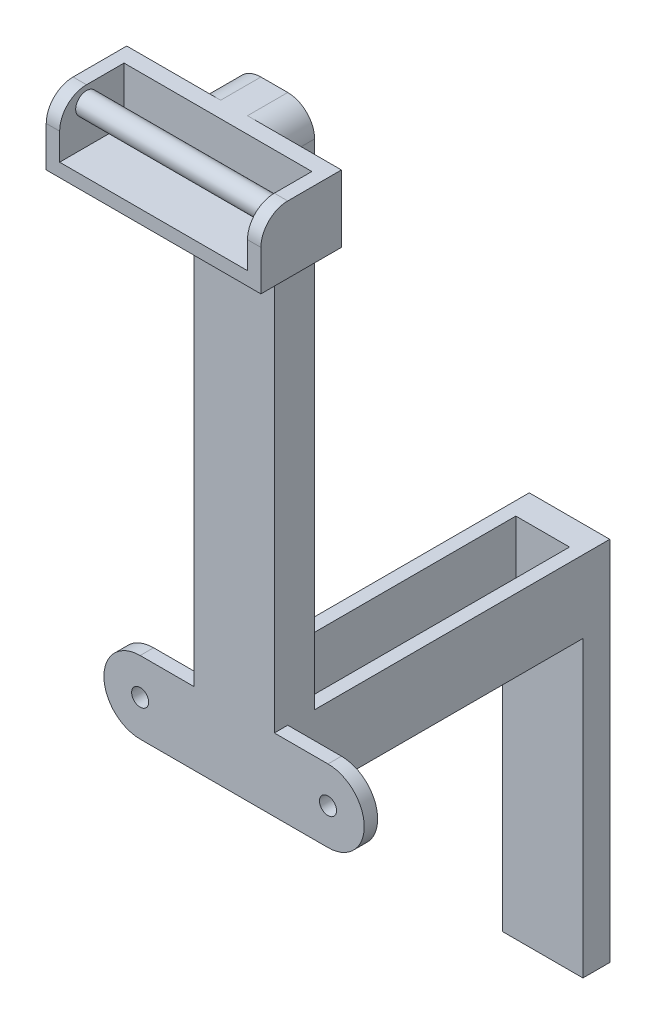
SolidWorks part; units mm, degrees
ref_plane "Front Plane" through (0, 0, 0) normal (0, 0, 1) x (1, 0, 0)
ref_plane "Top Plane" through (0, 0, 0) normal (0, 1, 0) x (1, 0, 0)
ref_plane "Right Plane" through (0, 0, 0) normal (1, 0, 0) x (0, 0, -1)
sketch "Sketch1" plane through (0, 0, 0) normal (0, 0, 1) x (1, 0, 0)
  line L0 (50, 212.065) -> (-20, 212.065) construction
  line L1 (30, -62.835) -> (0, -62.835)
  line L2 (30, -62.835) -> (30, 419.765)
  line L3 (30, 419.765) -> (0, 419.765)
  line L4 (0, -62.835) -> (0, 419.765)
  line L5 (30, -62.835) -> (0, 419.765) construction
  line L6 (30, 419.765) -> (0, -62.835) construction
  line L7 (50, 198.565) -> (-20, 198.565)
  line L8 (50, 225.565) -> (-20, 225.565)
  arc A0 (50, 198.565) -> (50, 225.565) centre (50, 212.065) ccw
  arc A1 (-20, 225.565) -> (-20, 198.565) centre (-20, 212.065) ccw
  point P0 (15, 178.465)
  point P7 (15, 212.065)
  dimension "D1" = 482.6
  dimension "D2" = 27
  dimension "D3" = 30
  dimension "D4" = 33.6
  dimension "D5" = 70
  dimension "D6" = 0
extrude "Extrude1" add sketch "Sketch1" along normal blind 15 contours L8 L2 L3 L4 | L7 A0 L8 L2 | L2 L8 L4 L7 | L8 A1 L7 L4 | L2 L7 L4 L1 region at (15, 67.865, 0) region at (15, 212.065, 0) region at (45.4498, 212.065, 0) region at (-15.4498, 212.065, 0) region at (15, 322.665, 0)
fillet "Fillet1" radius 10 4 edges at (30, -62.835, 7.5) (0, -62.835, 7.5) (0, 419.765, 7.5) (30, 419.765, 7.5)
sketch "Sketch2" plane through (0, 0, 0) normal (0, 0, -1) x (-1, 0, 0)
  line L0 (-50, 225.565) -> (-30, 225.565) construction
  line L1 (-50, 198.565) -> (-30, 198.565) construction
  line L2 (0, 198.565) -> (20, 198.565) construction
  line L3 (0, 225.565) -> (20, 225.565) construction
  line L4 (-50, 225.565) -> (-30, 225.565)
  line L5 (-50, 198.565) -> (-30, 198.565)
  line L6 (0, 198.565) -> (20, 198.565)
  line L7 (0, 225.565) -> (20, 225.565)
  line L8 (-30, 225.565) -> (-30, 198.565)
  line L9 (0, 225.565) -> (0, 198.565)
  arc A0 (20, 198.565) -> (20, 225.565) centre (20, 212.065) ccw construction
  arc A1 (-50, 225.565) -> (-50, 198.565) centre (-50, 212.065) ccw construction
  arc A2 (20, 198.565) -> (20, 225.565) centre (20, 212.065) ccw
  arc A3 (-50, 225.565) -> (-50, 198.565) centre (-50, 212.065) ccw
extrude "Extrude2" cut sketch "Sketch2" against normal blind 10
sketch "Sketch3" plane through (0, 0, 15) normal (0, 0, 1) x (1, 0, 0)
  line L0 (30, 407.265) -> (0, 407.265) construction
  line L1 (-25, 394.765) -> (55, 394.765)
  line L2 (-25, 394.765) -> (-25, 419.765)
  line L3 (-25, 419.765) -> (55, 419.765)
  line L4 (55, 394.765) -> (55, 419.765)
  line L5 (-25, 394.765) -> (55, 419.765) construction
  line L6 (-25, 419.765) -> (55, 394.765) construction
  line L7 (30, 225.565) -> (30, 409.765) construction
  line L8 (0, 225.565) -> (0, 409.765) construction
  line L9 (15, 407.265) -> (15, 419.765) construction
  line L10 (20, 419.765) -> (10, 419.765) construction
  point P0 (15, 407.265)
  dimension "D1" = 80
  dimension "D2" = 0
  dimension "D3" = 25
  dimension "D4" = 0
extrude "Extrude3" add sketch "Sketch3" along normal blind 30
sketch "Sketch5" plane through (0, 0, 45) normal (0, 0, 1) x (1, 0, 0)
  line L0 (55, 419.765) -> (-25, 419.765) construction
  line L1 (-20, 419.765) -> (50, 419.765)
  line L2 (-20, 419.765) -> (-20, 399.765)
  line L3 (-20, 399.765) -> (50, 399.765)
  line L4 (50, 419.765) -> (50, 399.765)
  line L5 (-25, 419.765) -> (-25, 394.765) construction
  line L6 (55, 394.765) -> (55, 419.765) construction
  line L7 (-25, 394.765) -> (55, 394.765) construction
  dimension "D1" = 5
  dimension "D2" = 5
  dimension "D3" = 5
extrude "Extrude4" cut sketch "Sketch5" against normal blind 24
fillet "Fillet2" radius 10 2 edges at (-22.5, 419.765, 45) (52.5, 419.765, 45)
sketch "Sketch6" plane through (50, 0, 0) normal (-1, 0, 0) x (0, 0, 1)
  circle A0 centre (35, 413.8477) radius 4.0292
extrude "Extrude5" add sketch "Sketch6" along normal up to next
sketch "Sketch7" plane through (0, 0, 0) normal (0, 0, -1) x (-1, 0, 0)
  line L0 (0, 198.565) -> (-30, 198.565)
  line L1 (-30, 198.565) -> (-30, -64.8073)
  line L2 (-30, -64.8073) -> (0, -64.8073)
  line L3 (0, -64.8073) -> (0, 198.565)
extrude "Extrude6" cut sketch "Sketch7" against normal through all
sketch "Sketch8" plane through (0, 0, 0) normal (0, 0, -1) x (-1, 0, 0)
  line L0 (-30, 198.565) -> (0, 198.565)
  line L1 (0, 198.565) -> (0, 225.565)
  line L2 (0, 225.565) -> (-5, 225.565)
  line L3 (-5, 225.565) -> (-5, 203.565)
  line L4 (-5, 203.565) -> (-25, 203.565)
  line L5 (-25, 203.565) -> (-25, 225.565)
  line L6 (-25, 225.565) -> (-30, 225.565)
  line L7 (-30, 198.565) -> (-30, 225.565) construction
  line L8 (-30, 198.565) -> (-30, 409.765) construction
  line L9 (-30, 225.565) -> (-30, 198.565)
  dimension "D1" = 5
  dimension "D2" = 5
  dimension "D3" = 5
extrude "Extrude7" add sketch "Sketch8" along normal blind 100
sketch "Sketch9" plane through (0, 0, -100) normal (0, 0, -1) x (-1, 0, 0)
  line L1 (-30, 225.565) -> (0, 225.565)
  line L2 (-30, 225.565) -> (-30, 88.9838)
  line L3 (-30, 88.9838) -> (0, 88.9838)
  line L4 (0, 225.565) -> (0, 88.9838)
extrude "Extrude8" add sketch "Sketch9" along normal blind 10
hole_wizard "1/4 (0.25) Diameter Hole1" positions "3DSketch1" profile "Sketch10" hole size "1/4" standard "Ansi Inch"
sketch3d "3DSketch1"
  line L0 (-20, 212.065, 15) -> (-20, 212.065, 10) construction
  line L1 (50, 212.065, 15) -> (50, 212.065, 10) construction
  point P0 (-20, 212.065, 10)
  point P4 (50, 212.065, 10)
sketch "Sketch10" plane through (-20, 212.065, 10) normal (1, 0, 0) x (0, 1, 0)
  line L0 (0, 0) -> (0, 11.9077)
  line L1 (0, 11.9077) -> (3.175, 10)
  line L2 (3.175, 10) -> (3.175, 0)
  line L5 (3.175, 0) -> (0, 0)
  line L10 (0, 11.9077) -> (-3.175, 10) construction
  line L11 (0, -6.35) -> (0, 107.95) construction
  dimension "Hole Dia." = 6.35
  dimension "Hole Depth" = 10
  dimension "Drill Angle" = 118
